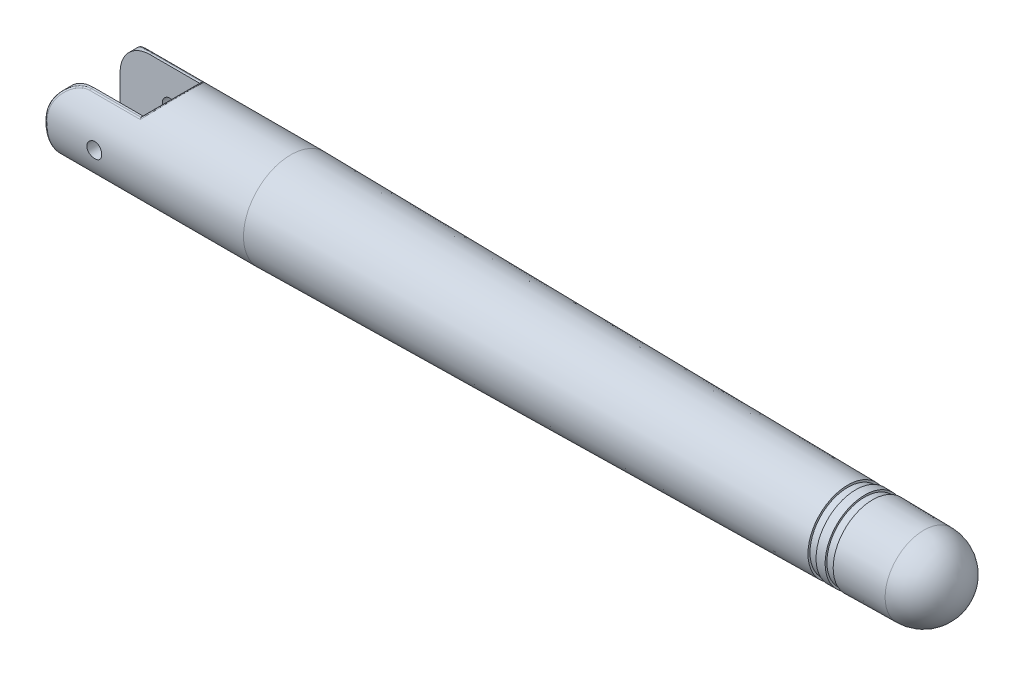
SolidWorks part; units mm, degrees
ref_plane "Спереди" through (0, 0, 0) normal (0, 0, 1) x (1, 0, 0)
ref_plane "Сверху" through (0, 0, 0) normal (0, 1, 0) x (1, 0, 0)
ref_plane "Справа" through (0, 0, 0) normal (1, 0, 0) x (0, 0, -1)
sketch "Эскиз1" plane through (0, 0, 0) normal (0, 0, 1) x (1, 0, 0)
  line L0 (0, 0) -> (87.5, 0) construction
  line L1 (0, 0) -> (0, 4.75)
  line L2 (0, 4.75) -> (20, 4.75)
  line L3 (20, 4.75) -> (76, 4.0019)
  line L4 (76, 4.0019) -> (76, 3.8)
  line L5 (76, 3.8) -> (76.8, 3.8)
  line L6 (76.8, 3.8) -> (76.8, 3.9912)
  line L7 (77.7, 3.9792) -> (77.7, 3.8)
  line L8 (77.7, 3.8) -> (78.5, 3.8)
  line L9 (78.5, 3.8) -> (78.5, 3.9685)
  line L10 (76.8, 3.9912) -> (77.7, 3.9792)
  line L11 (78.5, 3.9685) -> (83.6521, 3.8997)
  line L12 (0, 0) -> (87.5, 0)
  arc A0 (83.6521, 3.8997) -> (87.5, 0) centre (83.6, 0) cw
  dimension "D3" = 3.9
  dimension "D1" = 20
  dimension "D2" = 9.5
  dimension "D4" = 87.5
  dimension "D5" = 0.9
  dimension "D6" = 0.8
  dimension "D7" = 0.8
  dimension "D8" = 9
  dimension "D9" = 3.8
revolve "Повернуть1" add sketch "Эскиз1" angle 360 about L0
sketch "Эскиз2" plane through (0, 0, 0) normal (0, 1, 0) x (1, 0, 0)
  line L0 (0, 4.75) -> (0, -4.75) construction
  line L1 (0, -2.85) -> (8, -2.85)
  line L2 (0, -2.85) -> (0, 2.85)
  line L3 (0, 2.85) -> (8, 2.85)
  line L4 (8, -2.85) -> (8, 2.85)
  dimension "D1" = 5.7
  dimension "D2" = 8
extrude "Вырез-Вытянуть1" cut sketch "Эскиз2" along normal through all and the other way blind 3.5
sketch "Эскиз3" plane through (0, 0, 0) normal (0, 0, 1) x (1, 0, 0)
  line L0 (0, 0) -> (5, 0) construction
  line L1 (0, 3.8) -> (0, 3.55)
  line L2 (0, 3.8) -> (0, -4.75) construction
  line L4 (0, 3.55) -> (8, 3.55)
  line L5 (8, 3.55) -> (9.2, 4.75)
  line L6 (20, 4.75) -> (8, 4.75) construction
  line L7 (9.2, 4.75) -> (0, 4.75)
  line L8 (0, 4.75) -> (0, 3.8)
  circle A0 centre (5, 0) radius 0.75
  dimension "D2" = 1.5
  dimension "D1" = 5
  dimension "D3" = 0.25
  dimension "D4" = 8
  dimension "D5" = 45
extrude "Вырез-Вытянуть2" cut sketch "Эскиз3" against normal through all both and the other way through all
fillet "Скругление2" radius 3 2 edges at (0, 3.55, -3.003) (0, 3.55, 3.003)
fillet "Скругление1" radius 0.25 6 edges at (0, -4.75, 0) (5.5, 3.55, -3.1559) (9.2, 4.75, 0) (5.5, 3.55, 3.1559) (0.5333, 2.2574, -4.1793) (1.4815, 3.1373, 3.5665)
